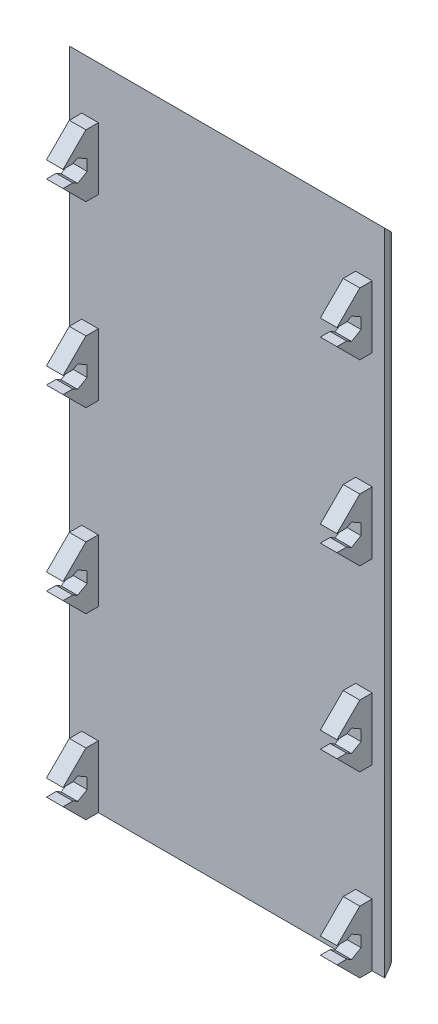
SolidWorks part; units mm, degrees
ref_plane "Front Plane" through (0, 0, 0) normal (0, 0, 1) x (1, 0, 0)
ref_plane "Top Plane" through (0, 0, 0) normal (0, 1, 0) x (1, 0, 0)
ref_plane "Right Plane" through (0, 0, 0) normal (1, 0, 0) x (0, 0, -1)
sketch "Sketch1" plane through (0, 0, 0) normal (0, 1, 0) x (1, 0, 0)
  line L0 (-9.2151, 0) -> (-9.2151, -10)
  line L1 (-9.2151, -10) -> (-5.2151, -10)
  line L2 (-5.2151, -10) -> (-5.2151, 0)
  line L3 (-5.2151, 0) -> (56.7849, 0)
  line L4 (56.7849, 0) -> (56.7849, -10)
  line L5 (56.7849, -10) -> (60.7849, -10)
  line L6 (60.7849, -10) -> (60.7849, 0)
  line L7 (60.7849, 0) -> (63.7849, 0)
  line L8 (-9.2151, 0) -> (-12.2151, 0)
  line L9 (-12.2151, 0) -> (-8.1737, 7)
  line L10 (-8.1737, 7) -> (59.7434, 7)
  line L11 (59.7434, 7) -> (63.7849, 0)
  line L12 (25.7849, 7) -> (25.7849, 0) construction
  dimension "D1" = 3
  dimension "D2" = 10
  dimension "D3" = 70
  dimension "D4" = 7
  dimension "D5" = 4
  dimension "D6" = 60
extrude "Boss-Extrude1" add sketch "Sketch1" along normal blind 156.5
sketch "Sketch4" plane through (60.7849, 0, 0) normal (1, 0, 0) x (0, 0, -1)
  line L0 (0, 156.5) -> (0, 0) construction
  line L1 (-37.5185, 156.5) -> (0, 156.5)
  line L2 (-37.5185, 156.5) -> (-37.5185, 144)
  line L3 (-37.5185, 144) -> (0, 144)
  line L4 (0, 156.5) -> (0, 144)
  line L5 (-37.5185, 156.5) -> (0, 144) construction
  line L6 (-37.5185, 144) -> (0, 156.5) construction
  line L7 (-10, 156.5) -> (0, 156.5) construction
  point P0 (-18.7592, 150.25)
  dimension "D1" = 12.5
extrude "Cut-Extrude1" cut sketch "Sketch4" against normal through all
sketch "Sketch5" plane through (60.7849, 0, 0) normal (1, 0, 0) x (0, 0, -1)
  line L0 (0, 156.5) -> (0, 0) construction
  line L1 (-33.3149, 129) -> (0, 129)
  line L2 (-33.3149, 129) -> (-33.3149, 101)
  line L3 (-33.3149, 101) -> (0, 101)
  line L4 (0, 129) -> (0, 101)
  line L5 (-33.3149, 129) -> (0, 101) construction
  line L6 (-33.3149, 101) -> (0, 129) construction
  line L7 (-10, 144) -> (0, 144) construction
  point P0 (-16.6574, 115)
  dimension "D1" = 28
  dimension "D2" = 15
extrude "Cut-Extrude2" cut sketch "Sketch5" against normal through all
sketch "Sketch6" plane through (0, 0, 0) normal (1, 0, 0) x (0, 0, -1)
  line L0 (-10, 144) -> (-10, 129) construction
  line L1 (-2.7, 137.8279) -> (-5, 139.1558)
  line L2 (-5, 139.1558) -> (-7.3, 137.8279)
  line L3 (-7.3, 137.8279) -> (-7.3, 135.1721)
  line L4 (-7.3, 135.1721) -> (-5, 133.8442)
  line L5 (-5, 133.8442) -> (-2.7, 135.1721)
  line L6 (-2.7, 135.1721) -> (-2.7, 137.8279)
  line L7 (-10, 144) -> (0, 144) construction
  line L8 (-6.15, 138.4919) -> (-10, 138.4919)
  line L9 (-6.15, 134.5081) -> (-10, 134.5081)
  line L10 (-10, 134.5081) -> (-10, 138.4919)
  circle A1 centre (-5, 136.5) radius 2.3 construction
  dimension "D1" = 4.6
  dimension "D2" = 7.5
  dimension "D3" = 5
extrude "Cut-Extrude3" cut sketch "Sketch6" against normal through all and the other way through all contours L10 L9 L4 L3 L2 L8 | L5 L6 L1 L2 L3 L4 region at (0, 136.5, 5) region at (0, 136.5, 8.5351)
pattern_linear "LPattern1" count 4 spacing 43 along (0, -1, 0) of "Cut-Extrude2", "Cut-Extrude3"
chamfer "Chamfer3" distance 7 angle 45 1 edges at (25.7849, 156.5, -7)
fillet "Fillet1" radius 8 2 edges at (-8.1737, 74.75, -7) (59.7434, 74.75, -7)
chamfer "Chamfer5" distance 7 angle 45 16 edges at (58.7849, 43, 10) (58.7849, 144, 10) (58.7849, 129, 10) (-7.2151, 144, 10) (-7.2151, 129, 10) (-7.2151, 101, 10) (-7.2151, 86, 10) (58.7849, 101, 10) (58.7849, 86, 10) (58.7849, 58, 10) (58.7849, 0, 10) (58.7849, 15, 10) (-7.2151, 0, 10) (-7.2151, 15, 10) (-7.2151, 58, 10) (-7.2151, 43, 10)
sketch "Sketch7" plane through (0, 0, -7) normal (0, 0, -1) x (-1, 0, 0)
  line L8 (3.5549, 82.737) -> (-11.316, 82.737) construction
  line L14 (-11.316, 128.6101) -> (-40.2538, 128.6101) construction
  line L20 (-11.316, 128.6101) -> (-11.316, 82.737) construction
  line L22 (-40.2538, 128.6101) -> (-40.2538, 82.737) construction
  line L23 (-11.316, 82.737) -> (-40.2538, 82.737) construction
  line L24 (3.5549, 0) -> (3.5549, 149.5) construction
  line L25 (-11.316, 127.6101) -> (-11.316, 116.1874)
  line L26 (-12.316, 128.6101) -> (-39.2538, 128.6101)
  line L27 (-11.316, 115.6101) -> (-40.2538, 115.6101) construction
  line L28 (-40.2538, 127.6101) -> (-40.2538, 115.6101)
  line L29 (-40.2538, 82.737) -> (-55.1246, 82.737) construction
  line L30 (-55.1246, 149.5) -> (-55.1246, 0) construction
  line L31 (-11.316, 149.5) -> (-11.316, 128.6101) construction
  line L32 (3.5549, 149.5) -> (-55.1246, 149.5) construction
  line L35 (-11.316, 107.5272) -> (-17.816, 103.7744)
  line L38 (-25.316, 99.4443) -> (-39.7538, 91.1086)
  line L39 (-11.316, 107.5272) -> (-11.316, 93.237)
  line L40 (-40.2538, 90.2426) -> (-40.2538, 82.737)
  line L41 (-40.2538, 82.737) -> (-32.316, 87.3199)
  line L42 (-32.316, 87.3199) -> (-32.316, 93.237) construction
  line L43 (-18.316, 102.9084) -> (-18.316, 93.237)
  line L44 (-11.316, 93.237) -> (-32.316, 93.237) construction
  line L45 (-25.316, 99.4443) -> (-25.316, 93.237)
  line L46 (-18.316, 93.237) -> (-25.316, 93.237) construction
  line L47 (-39.7538, 107.2744) -> (-18.566, 119.5072)
  line L48 (-40.2538, 115.6101) -> (-40.2538, 106.9857) construction
  line L49 (-11.316, 82.737) -> (-40.2538, 82.737) construction
  line L50 (-40.2538, 106.4084) -> (-40.2538, 100.5631)
  line L51 (-32.316, 87.3199) -> (-30.9714, 88.0962)
  line L52 (-11.816, 115.3214) -> (-31.566, 103.9187)
  line L53 (-33.2538, 121.1101) -> (-33.2538, 119.3988)
  line L54 (-31.566, 103.0527) -> (-25.316, 99.4443)
  line L55 (-32.316, 95.4028) -> (-39.7538, 99.6971)
  line L56 (-33.5038, 118.9657) -> (-40.2538, 115.0686)
  line L57 (-40.2538, 115.0686) -> (-40.2538, 115.6101)
  line L58 (-32.7538, 121.6101) -> (-18.816, 121.6101)
  line L59 (-18.316, 121.1101) -> (-18.316, 119.9402)
  line L60 (-11.316, 121.6101) -> (-18.316, 121.6101) construction
  line L61 (-33.2538, 121.6101) -> (-40.2538, 121.6101) construction
  line L62 (-40.2538, 128.6101) -> (-11.316, 128.6101) construction
  line L63 (-11.316, 128.6101) -> (-11.316, 82.737) construction
  arc A7 (-11.316, 93.237) -> (-32.316, 93.237) centre (-21.816, 93.237) cw
  arc A8 (-18.316, 93.237) -> (-25.316, 93.237) centre (-21.816, 93.237) cw
  arc A9 (-17.816, 103.7744) -> (-18.316, 102.9084) centre (-17.316, 102.9084) ccw
  arc A10 (-11.816, 115.3214) -> (-11.316, 116.1874) centre (-12.316, 116.1874) ccw
  arc A11 (-11.316, 127.6101) -> (-12.316, 128.6101) centre (-12.316, 127.6101) ccw
  arc A12 (-39.7538, 91.1086) -> (-40.2538, 90.2426) centre (-39.2538, 90.2426) ccw
  arc A13 (-39.2538, 128.6101) -> (-40.2538, 127.6101) centre (-39.2538, 127.6101) ccw
  arc A14 (-40.2538, 106.4084) -> (-39.7538, 107.2744) centre (-39.2538, 106.4084) cw
  arc A15 (-39.7538, 99.6971) -> (-40.2538, 100.5631) centre (-39.2538, 100.5631) cw
  arc A16 (-32.7538, 121.6101) -> (-33.2538, 121.1101) centre (-32.7538, 121.1101) ccw
  arc A17 (-33.5038, 118.9657) -> (-33.2538, 119.3988) centre (-33.7538, 119.3988) ccw
  arc A18 (-18.316, 121.1101) -> (-18.816, 121.6101) centre (-18.816, 121.1101) ccw
  arc A19 (-18.566, 119.5072) -> (-18.316, 119.9402) centre (-18.816, 119.9402) ccw
  arc A20 (-31.566, 103.0527) -> (-31.566, 103.9187) centre (-31.316, 103.4857) cw
  point P59 (-40.2538, 106.9857)
  point P63 (-40.2538, 99.9857)
  dimension "D11" = 7
  dimension "D12" = 30
  dimension "D10" = 7
  dimension "D14" = 0.5
  dimension "D16" = 7
  dimension "D6" = 7
  dimension "D13" = 1
  dimension "D2" = 1
  dimension "0.5" = 1
  dimension "D18" = 1
  dimension "D4" = 0.5
  dimension "D1" = 7
  dimension "D3" = 7
  dimension "D5" = 7
  dimension "D7" = 7
  dimension "D8" = 7
  dimension "D9" = 7
  dimension "D15" = 30
  dimension "D17" = 7
extrude "Cut-Extrude4" cut sketch "Sketch7" against normal blind 1 contours L54 A20 L52 A10 L25 A11 L26 A13 L28 L57 L56 L53 L58 L59 L47 A14 L50 A15 L55 L38 | L38 A12 L40 L41 L51 A7 L39 L35 A9 L43 A8 L45 region at (11.7564, 121.8988, -7) region at (25.697, 96.3406, -7)
sketch "Sketch8" plane through (0, 0, -7) normal (0, 0, -1) x (-1, 0, 0)
  line L0 (-40.2538, 128.6101) -> (-40.2538, 8.6101) construction
  line L1 (-55.1246, 149.5) -> (-55.1246, 0) construction
  line L2 (-25.7849, 128.6101) -> (-55.1246, 128.6101) construction
  line L3 (-12.316, 128.6101) -> (-39.2538, 128.6101) construction
  line L5 (-40.2538, 127.6101) -> (-40.2538, 115.0686) construction
  text T0 "DREAm" font "VALORANT" height in points 48
  dimension "D1" = 120
extrude "Cut-Extrude5" cut sketch "Sketch8" against normal blind 1
fillet "Fillet2" radius 0.5 2 edges at (32.316, 95.4028, -6.5) (25.316, 99.4443, -6.5)
